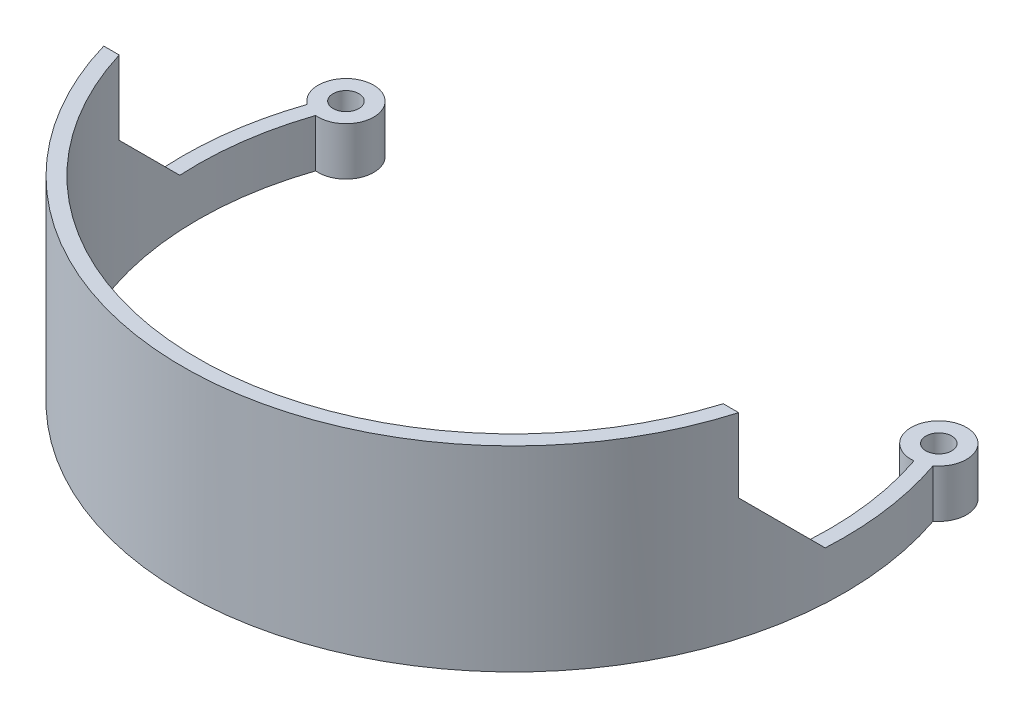
SolidWorks part; units mm, degrees
ref_plane "前视基准面" through (0, 0, 0) normal (0, 0, 1) x (1, 0, 0)
ref_plane "上视基准面" through (0, 0, 0) normal (0, 1, 0) x (1, 0, 0)
ref_plane "右视基准面" through (0, 0, 0) normal (1, 0, 0) x (0, 0, -1)
sketch "草图1" plane through (0, 0, 0) normal (0, 1, 0) x (1, 0, 0)
  line L0 (-85.9375, -25) -> (85.9375, -25) construction
  line L1 (-85.9375, -25) -> (-81.7634, -25)
  line L2 (81.7634, -25) -> (85.9375, -25)
  arc A0 (83.1987, 32.9883) -> (79.5039, 31.4543) centre (80.25, 34.8739) ccw
  circle A1 centre (0, 0) radius 87.5 construction
  circle A2 centre (-80.25, 34.8739) radius 3.5
  arc A3 (-75.2965, 40.5053) -> (-77.241, 36.6616) centre (0, 0) ccw construction
  arc A4 (-78.8992, 42.2512) -> (-80.8834, 38.3161) centre (0, 0) ccw construction
  arc A5 (-80.9872, 27.4102) -> (-84.7217, 28.8528) centre (-80.25, 34.8739) ccw
  arc A6 (84.7217, 28.8528) -> (80.9872, 27.4102) centre (80.25, 34.8739) ccw
  circle A7 centre (-80.25, 34.8739) radius 2.25
  circle A8 centre (80.25, 34.8739) radius 2.25
  arc A9 (78.8992, 42.2512) -> (-78.8992, 42.2512) centre (0, 0) ccw construction
  arc A10 (75.2965, 40.5053) -> (-75.2965, 40.5053) centre (0, 0) ccw construction
  arc A11 (-80.8834, 38.3161) -> (-81.6632, 36.6247) centre (0, 0) ccw construction
  arc A12 (-84.7217, 28.8528) -> (84.7217, 28.8528) centre (0, 0) ccw
  arc A13 (-81.6632, 36.6247) -> (-82.4942, 34.7125) centre (0, 0) ccw construction
  arc A14 (-82.4942, 34.7125) -> (-83.1987, 32.9883) centre (0, 0) ccw construction
  arc A15 (-78.8162, 33.1399) -> (-79.5039, 31.4543) centre (0, 0) ccw construction
  arc A16 (-80.9872, 27.4102) -> (80.9872, 27.4102) centre (0, 0) ccw
  arc A17 (-77.241, 36.6616) -> (-78.0041, 35.0088) centre (0, 0) ccw construction
  arc A18 (-78.0041, 35.0088) -> (-78.8162, 33.1399) centre (0, 0) ccw construction
  arc A19 (-83.1987, 32.9883) -> (-84.7217, 28.8528) centre (0, 0) ccw construction
  arc A20 (-79.5039, 31.4543) -> (-80.9872, 27.4102) centre (0, 0) ccw construction
  arc A21 (80.8834, 38.3161) -> (78.8992, 42.2512) centre (0, 0) ccw construction
  arc A22 (77.241, 36.6616) -> (75.2965, 40.5053) centre (0, 0) ccw construction
  arc A23 (78.0041, 35.0088) -> (77.241, 36.6616) centre (0, 0) ccw construction
  arc A24 (79.5039, 31.4543) -> (78.8162, 33.1399) centre (0, 0) ccw construction
  arc A25 (78.8162, 33.1399) -> (78.0041, 35.0088) centre (0, 0) ccw construction
  arc A26 (82.4942, 34.7125) -> (81.6632, 36.6247) centre (0, 0) ccw construction
  arc A27 (81.6632, 36.6247) -> (80.8834, 38.3161) centre (0, 0) ccw construction
  arc A28 (83.1987, 32.9883) -> (82.4942, 34.7125) centre (0, 0) ccw construction
  arc A29 (81.5805, 31.6366) -> (83.1987, 32.9883) centre (80.25, 34.8739) ccw
  arc A30 (79.5039, 31.4543) -> (81.5805, 31.6366) centre (80.25, 34.8739) ccw
  arc A31 (-82.9416, 27.8735) -> (-80.9872, 27.4102) centre (-80.25, 34.8739) ccw construction
  arc A32 (-84.7217, 28.8528) -> (-82.9416, 27.8735) centre (-80.25, 34.8739) ccw construction
  arc A33 (82.9416, 27.8735) -> (84.7217, 28.8528) centre (80.25, 34.8739) ccw construction
  arc A34 (80.9872, 27.4102) -> (82.9416, 27.8735) centre (80.25, 34.8739) ccw construction
  arc A35 (80.9872, 27.4102) -> (79.5039, 31.4543) centre (0, 0) ccw construction
  arc A36 (84.7217, 28.8528) -> (83.1987, 32.9883) centre (0, 0) ccw construction
  dimension "D1" = 7
  dimension "D2" = 175
  dimension "D3" = 7
  dimension "D5" = 2
  dimension "D6" = 2
  dimension "D7" = 4
  dimension "D8" = 4
  dimension "D9" = 4.5
  dimension "D10" = 4.5
  dimension "D4" = 160.5
  dimension "D11" = 25
extrude "凸台-拉伸3" add sketch "草图1" along normal blind 3 contours A0 A30 A29 A8 | A16 L2 A12 A6 A30 A0 A29 | A16 A5 A12 L1 A2 | A2 A7 | A16 L1 A12 L2 region at (-88.7831, 0, -2.0043) region at (-83.8504, 0, 26.8358) region at (83.8504, 0, 24.3058) region at (82.4303, 0, -32.2637) region at (-83.651, 0, -34.8739)
extrude "凸台-拉伸4" add sketch "草图1<9>" along normal blind 10 from surface contours A16 A5 A12 L1 A2 | A16 L1 A12 L2 | A16 L2 A12 A6 A30 A0 A29 region at (-88.7831, 0, -2.0043) region at (-83.8504, 0, 26.8358) region at (83.8504, 0, 24.3058) starting at face at (80.25, 3, -32.6239)
sketch "草图1<9>" plane through (0, 0, 0) normal (0, 1, 0) x (1, 0, 0) same geometry as "草图1"
extrude "凸台-拉伸5" add sketch "草图1<10>" along normal blind 40 from surface contours A16 L1 A12 L2 region at (-83.8504, 0, 26.8358) starting at face at (-80.25, 13, -31.3739)
sketch "草图1<10>" plane through (0, 0, 0) normal (0, 1, 0) x (1, 0, 0) same geometry as "草图1"
chamfer "倒角1" distance 20 angle 45 2 edges at (-83.8504, 13, 25) (83.8504, 13, 25)
